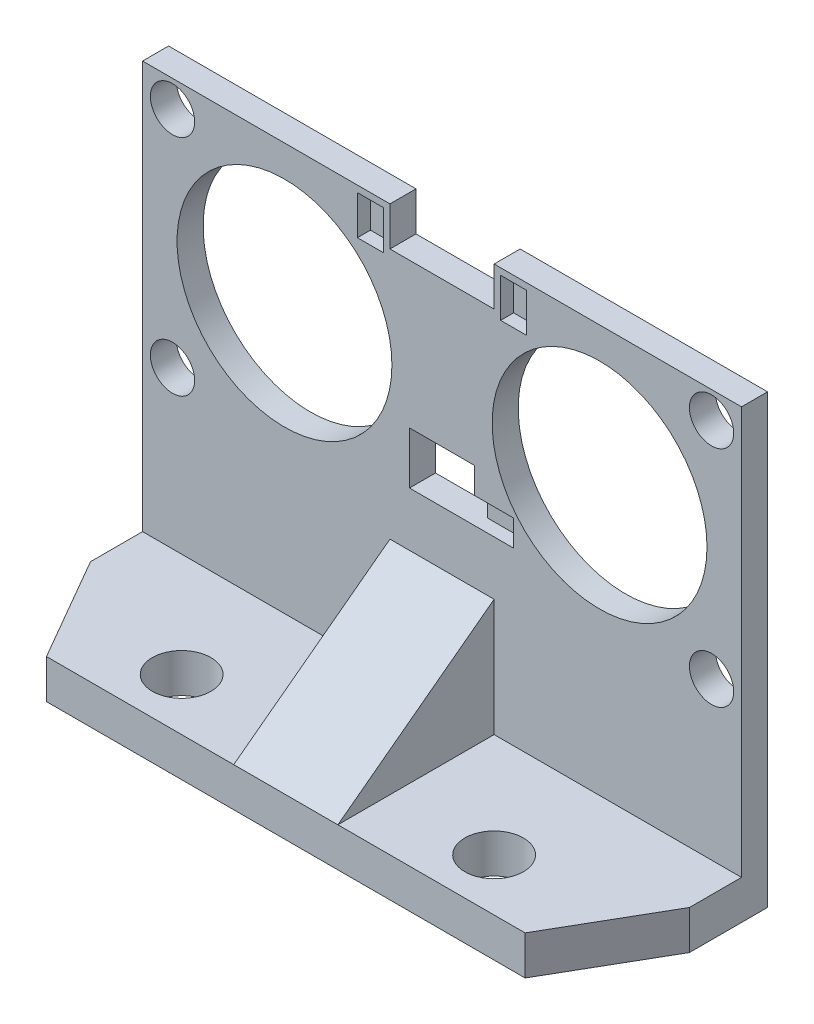
SolidWorks part; units mm, degrees
material "ABS"
ref_plane "前基準面" through (0, 0, 0) normal (0, 0, 1) x (1, 0, 0)
ref_plane "上基準面" through (0, 0, 0) normal (0, 1, 0) x (1, 0, 0)
ref_plane "右基準面" through (0, 0, 0) normal (1, 0, 0) x (0, 0, -1)
sketch "草圖1" plane through (0, 0, 0) normal (0, 0, 1) x (1, 0, 0)
  line L1 (-23, -10.65) -> (23, -10.65)
  line L2 (-23, -10.65) -> (-23, 10.65)
  line L3 (-23, 10.65) -> (23, 10.65)
  line L4 (23, -10.65) -> (23, 10.65)
  line L5 (-23, -10.65) -> (23, 10.65) construction
  line L6 (-23, 10.65) -> (23, -10.65) construction
  point P0 (0, 0)
  dimension "D1" = 46
  dimension "D2" = 21.3
extrude "填料-伸長1" add sketch "草圖1" along normal blind 2
sketch "草圖2" plane through (0, 0, 2) normal (0, 0, 1) x (1, 0, 0)
  line L0 (-12.1, 0) -> (12.1, 0) construction
  circle A0 centre (-12.1, 0) radius 8.25
  circle A1 centre (12.1, 0) radius 8.25
  point P4 (0, 0)
  dimension "D1" = 24.2
  dimension "D2" = 16.5
extrude "除料-伸長1" cut sketch "草圖2" against normal through all
sketch "草圖3" plane through (0, 0, 2) normal (0, 0, 1) x (1, 0, 0)
  line L0 (0, 0) -> (0, 9.15) construction
  line L1 (23, 10.65) -> (-23, 10.65) construction
  line L2 (-4, 7.65) -> (4, 7.65)
  line L3 (-4, 7.65) -> (-4, 10.65)
  line L4 (-4, 10.65) -> (4, 10.65)
  line L5 (4, 7.65) -> (4, 10.65)
  line L6 (-4, 7.65) -> (4, 10.65) construction
  line L7 (-4, 10.65) -> (4, 7.65) construction
  dimension "D1" = 8
  dimension "D2" = 3
extrude "除料-伸長2" cut sketch "草圖3" against normal through all
sketch "草圖4" plane through (0, 0, 2) normal (0, 0, 1) x (1, 0, 0)
  line L0 (0, 0) -> (0, -5.5) construction
  line L2 (-2.5, -3.5) -> (2.5, -3.5)
  line L3 (-2.5, -3.5) -> (-2.5, -7.5)
  line L4 (-2.5, -7.5) -> (2.5, -7.5)
  line L5 (2.5, -3.5) -> (2.5, -7.5)
  line L6 (-2.5, -3.5) -> (2.5, -7.5) construction
  line L7 (-2.5, -7.5) -> (2.5, -3.5) construction
  dimension "D1" = 5
  dimension "D2" = 4
  dimension "D3" = 5.5
extrude "除料-伸長3" cut sketch "草圖4" against normal through all
sketch "草圖5" plane through (0, 0, 2) normal (0, 0, 1) x (1, 0, 0)
  line L0 (0, 0) -> (0, 8.65) construction
  line L1 (2.5, -7.5) -> (5.5, -7.5)
  line L2 (2.5, -7.5) -> (2.5, -5.5)
  line L3 (2.5, -5.5) -> (5.5, -5.5)
  line L4 (5.5, -7.5) -> (5.5, -5.5)
  line L5 (-5.5, 8.65) -> (5.5, 8.65) construction
  line L6 (23, 10.65) -> (4, 10.65) construction
  line L7 (-4.5, 10.15) -> (-6.5, 10.15)
  line L8 (-4.5, 10.15) -> (-4.5, 7.15)
  line L9 (-4.5, 7.15) -> (-6.5, 7.15)
  line L10 (-6.5, 10.15) -> (-6.5, 7.15)
  line L11 (-4.5, 10.15) -> (-6.5, 7.15) construction
  line L12 (-4.5, 7.15) -> (-6.5, 10.15) construction
  line L13 (6.5, 10.15) -> (4.5, 10.15)
  line L14 (6.5, 10.15) -> (6.5, 7.15)
  line L15 (6.5, 7.15) -> (4.5, 7.15)
  line L16 (4.5, 10.15) -> (4.5, 7.15)
  line L17 (6.5, 10.15) -> (4.5, 7.15) construction
  line L18 (6.5, 7.15) -> (4.5, 10.15) construction
  point P10 (0, 8.65)
  dimension "D1" = 2
  dimension "D2" = 3
  dimension "D3" = 2
  dimension "D4" = 3
  dimension "D5" = 11
  dimension "D6" = 0.5
extrude "除料-伸長4" cut sketch "草圖5" against normal blind 1
sketch "草圖8" plane through (0, -10.65, 0) normal (0, -1, 0) x (1, 0, 0)
  line L1 (-23, 2) -> (23, 2)
  line L2 (-23, 2) -> (-23, 0)
  line L3 (-23, 0) -> (23, 0)
  line L4 (23, 2) -> (23, 0)
extrude "填料-伸長2" add sketch "草圖8" along normal blind 10
sketch "草圖9" plane through (0, -20.65, 0) normal (0, -1, 0) x (1, 0, 0)
  line L1 (-23, 0) -> (23, 0)
  line L2 (-23, 0) -> (-23, 14)
  line L3 (-23, 14) -> (23, 14)
  line L4 (23, 0) -> (23, 14)
  dimension "D1" = 14
extrude "填料-伸長3" add sketch "草圖9" along normal blind 3
hole_wizard "M3 餘隙孔1" positions "草圖6" profile "草圖7" hole size "M3" standard "Ansi Metric" end condition through all
sketch "草圖6" plane through (0, 0, 2) normal (0, 0, 1) x (1, 0, 0)
  line L1 (-20.7, -8.6) -> (20.7, -8.6) construction
  line L2 (-20.7, -8.6) -> (-20.7, 8.6) construction
  line L3 (-20.7, 8.6) -> (20.7, 8.6) construction
  line L4 (20.7, -8.6) -> (20.7, 8.6) construction
  line L5 (-20.7, -8.6) -> (20.7, 8.6) construction
  line L6 (-20.7, 8.6) -> (20.7, -8.6) construction
  point P1 (20.7, 8.6)
  point P112 (-20.7, -8.6)
  point P113 (-20.7, 8.6)
  point P114 (20.7, -8.6)
  dimension "D1" = 17.2
  dimension "D2" = 41.4
sketch "草圖7" plane through (20.7, 8.6, 2) normal (1, 0, 0) x (0, -1, 0)
  line L0 (0, 0) -> (0, 2)
  line L1 (0, 2) -> (1.7, 2)
  line L2 (1.7, 2) -> (1.7, 0)
  line L5 (1.7, 0) -> (0, 0)
  line L11 (0, -6.35) -> (0, 107.95) construction
  dimension "貫穿孔直徑" = 3.4
  dimension "貫穿孔深度" = 2
hole_wizard "M4 餘隙孔1" positions "草圖10" profile "草圖11" hole size "M4" standard "Ansi Metric" end condition through all
sketch "草圖10" plane through (0, -20.65, 0) normal (0, 1, 0) x (1, 0, 0)
  line L0 (0, -14) -> (0, -10) construction
  line L1 (23, -14) -> (-23, -14) construction
  line L4 (-12, -10) -> (12, -10) construction
  point P8 (-12, -10)
  point P9 (12, -10)
  dimension "D1" = 24
  dimension "D2" = 4
sketch "草圖11" plane through (12, -20.65, 10) normal (1, 0, 0) x (0, 0, 1)
  line L0 (0, 0) -> (0, 3)
  line L1 (0, 3) -> (2.25, 3)
  line L2 (2.25, 3) -> (2.25, 0)
  line L5 (2.25, 0) -> (0, 0)
  line L11 (0, -6.35) -> (0, 107.95) construction
  dimension "貫穿孔直徑" = 4.5
  dimension "貫穿孔深度" = 3
sketch "草圖13" plane through (0, 0, 0) normal (1, 0, 0) x (0, 0, -1)
  line L0 (-2, -11.65) -> (-14, -20.65)
  line L1 (-2, -20.65) -> (-2, 10.65) construction
  line L2 (-2, -20.65) -> (-14, -20.65) construction
  dimension "D1" = 9
rib "肋材1" sketch "草圖13" sketch "草圖13" thickness 8 extrusion direction parallel to sketch draft on no parameters "D1"=8
chamfer "導角1" distance 8 angle 30 2 edges at (-23, -22.15, 14) (23, -22.15, 14) first distance on face at (-23, -11.2167, 5.3333) first distance on face at (23, -11.2167, 5.3333)
